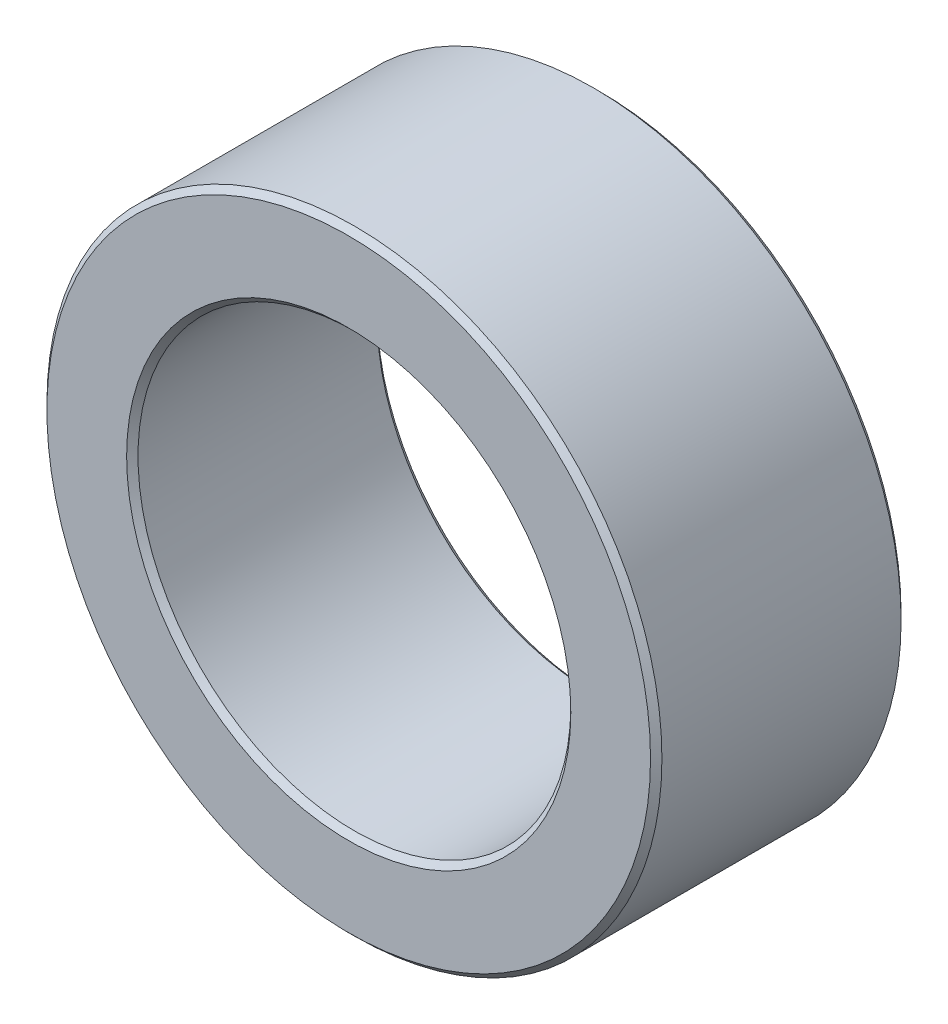
SolidWorks part; units mm, degrees
material "1.0037 (S235JR)"
ref_plane "E_Rechts" through (0, 0, 0) normal (0, 0, 1) x (1, 0, 0)
ref_plane "E_Oben" through (0, 0, 0) normal (0, 1, 0) x (1, 0, 0)
ref_plane "E_Vorne" through (0, 0, 0) normal (1, 0, 0) x (0, 0, -1)
ref_axis "A_Drehachse" through (0, 0, -88.99) along (0, 0, 1)
sketch "Skizze1" plane through (0, 0, 0) normal (0, 0, 1) x (1, 0, 0)
  circle A0 centre (0, 0) radius 19
  circle A1 centre (0, 0) radius 27
  dimension "D1" = 54
  dimension "D2" = 38
extrude "Aufsatz-Linear austragen1" add sketch "Skizze1" along normal mid plane 22
chamfer "Fase1" distance 0.5 angle 45 4 edges at (19, 0, -11) (27, 0, -11) (27, 0, 11) (19, 0, 11)
